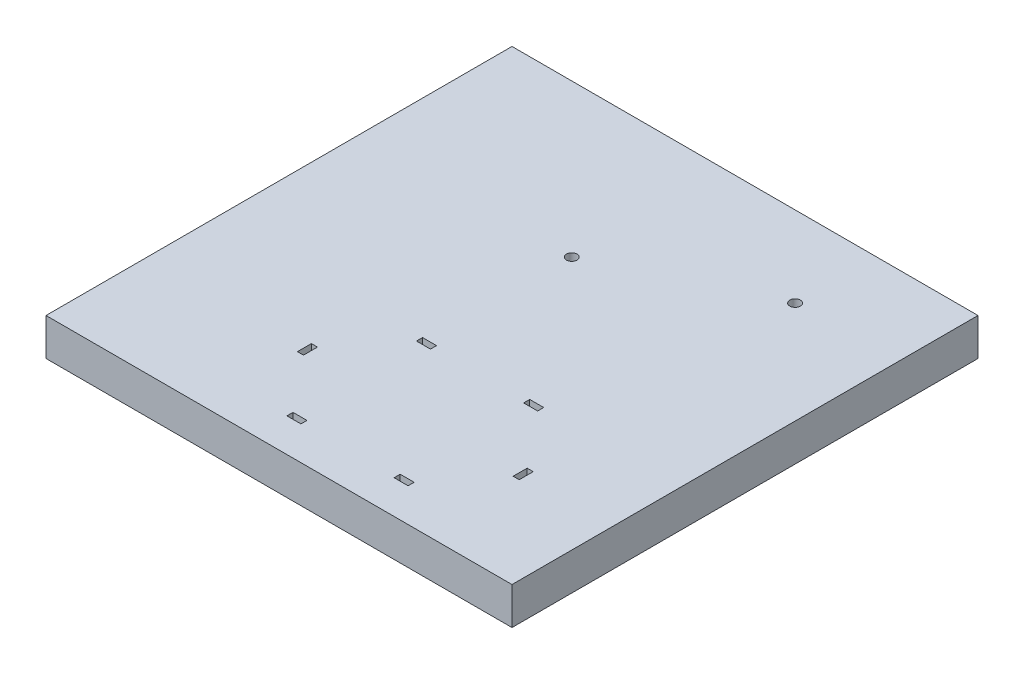
SolidWorks part; units mm, degrees
ref_plane "Front Plane" through (0, 0, 0) normal (0, 0, 1) x (1, 0, 0)
ref_plane "Top Plane" through (0, 0, 0) normal (0, 1, 0) x (1, 0, 0)
ref_plane "Right Plane" through (0, 0, 0) normal (1, 0, 0) x (0, 0, -1)
sketch "Sketch1" plane through (0, 0, 0) normal (0, 1, 0) x (1, 0, 0)
  line L0 (-66.0627, 0) -> (65.2437, 0) construction
  line L1 (-50, 50) -> (50, 50)
  line L2 (-50, 50) -> (-50, -50)
  line L3 (-50, -50) -> (50, -50)
  line L4 (50, 50) -> (50, -50)
  line L5 (7.5, -15) -> (7.5, -41.5) construction
  line L6 (-15, -15) -> (30, -15) construction
  line L7 (-15, -15) -> (-15, -41.5) construction
  line L8 (-15, -41.5) -> (30, -41.5) construction
  line L9 (30, -15) -> (30, -41.5) construction
  line L10 (-15.21, 35.09) -> (30, 35.09) construction
  line L11 (-15.21, 35.09) -> (-15.21, 15) construction
  line L12 (-15.21, 15) -> (30, 15) construction
  line L13 (30, 35.09) -> (30, 15) construction
  line L14 (-15.21, 35.09) -> (30, 15) construction
  line L15 (-15.21, 15) -> (30, 35.09) construction
  line L16 (-15, -28.25) -> (30, -28.25) construction
  line L17 (-5.5, -42.8) -> (-2.5, -42.8)
  line L18 (-5.5, -15) -> (-2.5, -15)
  line L19 (-5.5, -15) -> (-5.5, -13.7)
  line L20 (-5.5, -13.7) -> (-2.5, -13.7)
  line L21 (-2.5, -15) -> (-2.5, -13.7)
  line L22 (-2.5, -41.5) -> (-2.5, -42.8)
  line L23 (-5.5, -41.5) -> (-2.5, -41.5)
  line L24 (-5.5, -41.5) -> (-5.5, -42.8)
  line L25 (20.5, -15) -> (20.5, -13.7)
  line L26 (20.5, -13.7) -> (17.5, -13.7)
  line L27 (20.5, -15) -> (17.5, -15)
  line L28 (17.5, -15) -> (17.5, -13.7)
  line L29 (20.5, -41.5) -> (20.5, -42.8)
  line L30 (17.5, -41.5) -> (17.5, -42.8)
  line L31 (20.5, -41.5) -> (17.5, -41.5)
  line L32 (20.5, -42.8) -> (17.5, -42.8)
  line L33 (31.3, -29.75) -> (30, -29.75)
  line L34 (-16.3, -26.75) -> (-15, -26.75)
  line L35 (-16.3, -26.75) -> (-16.3, -29.75)
  line L36 (-16.3, -29.75) -> (-15, -29.75)
  line L37 (-15, -26.75) -> (-15, -29.75)
  line L38 (31.3, -26.75) -> (30, -26.75)
  line L39 (31.3, -26.75) -> (31.3, -29.75)
  line L40 (30, -26.75) -> (30, -29.75)
  circle A2 centre (28.07, 32.68) radius 1.13
  circle A3 centre (-4.44, 17.26) radius 1.13
  point P4 (50, 0)
  point P6 (0, 50)
  point P23 (7.395, 25.045)
  point P46 (-15, -28.25)
  dimension "D5" = 20
  dimension "D17" = 2.26
  dimension "D18" = 2.26
  dimension "D1" = 100
  dimension "D2" = 100
  dimension "D3" = 26.5
  dimension "D4" = 45
  dimension "D6" = 15
  dimension "D7" = 20
  dimension "D8" = 1.3
  dimension "D9" = 3
  dimension "D13" = 45.21
  dimension "D14" = 20.09
  dimension "D15" = 15
  dimension "D16" = 20
  dimension "D19" = 15.42
  dimension "D20" = 17.68
  dimension "D21" = 32.51
  dimension "D22" = 1.93
extrude "Boss-Extrude1" add sketch "Sketch1" along normal blind 8
